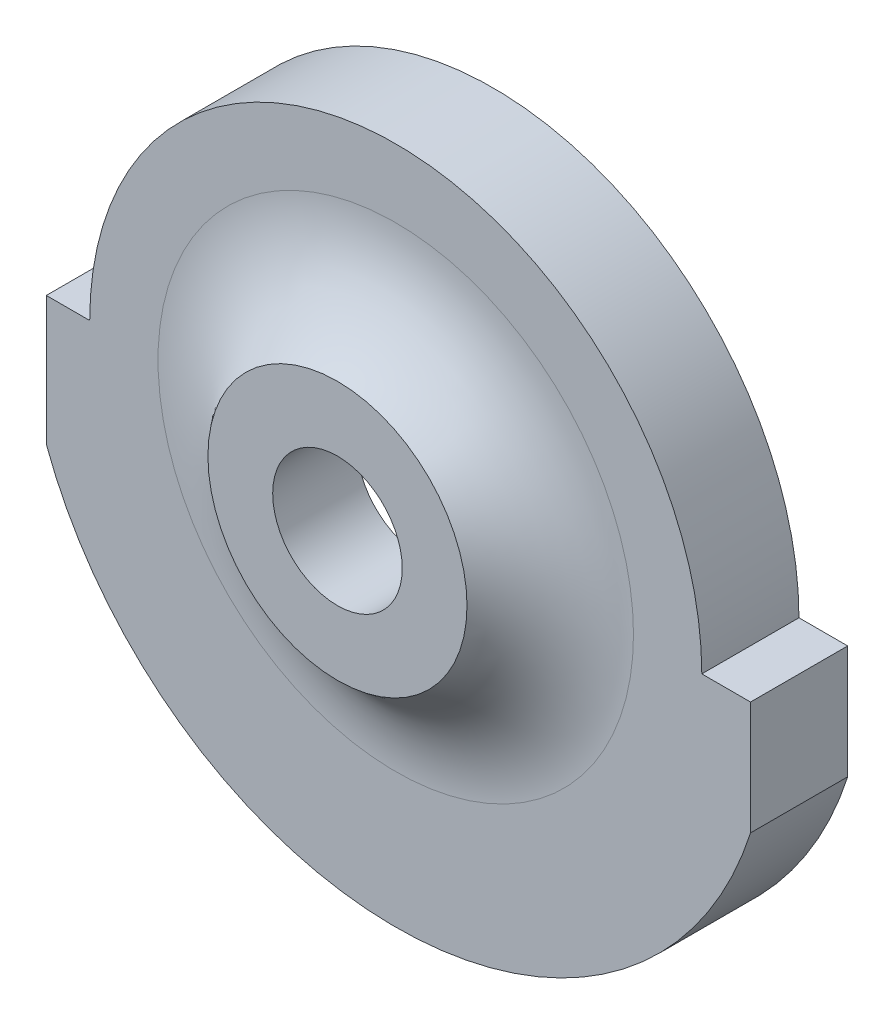
SolidWorks part; units mm, degrees
ref_plane "Front Plane" through (0, 0, 0) normal (0, 0, 1) x (1, 0, 0)
ref_plane "Top Plane" through (0, 0, 0) normal (0, 1, 0) x (1, 0, 0)
ref_plane "Right Plane" through (0, 0, 0) normal (1, 0, 0) x (0, 0, -1)
sketch "Sketch1" plane through (0, 0, 0) normal (0, 0, 1) x (1, 0, 0)
  line L0 (-8.55, 0) -> (8.55, 0) construction
  line L1 (-8.55, 0) -> (-16.55, 0)
  line L2 (8.55, 0) -> (16.55, 0)
  line L3 (-16.55, 0) -> (-16.55, 3.5)
  line L5 (-16.55, 3.5) -> (-10.9545, 3.5)
  line L6 (16.55, 0) -> (16.55, 3.5)
  line L7 (10.9545, 3.5) -> (16.55, 3.5)
  arc A0 (8.55, 0) -> (-8.55, 0) centre (0, 0) ccw
  arc A1 (10.9545, 3.5) -> (-10.9545, 3.5) centre (0, 0) ccw
  dimension "D1" = 17.1
  dimension "D3" = 23
  dimension "D2" = 3.5
extrude "Boss-Extrude1" add sketch "Sketch1" against normal blind 15.3
ref_plane "Plane1" through (0, 0, -6.3) normal (0, 0, 1) x (1, 0, 0)
sketch "Sketch2" plane through (0, 0, -6.3) normal (0, 0, 1) x (1, 0, 0)
  circle A0 centre (0, 0) radius 9.3
  dimension "D1" = 18.6
extrude "Cut-Extrude1" cut sketch "Sketch2" against normal blind 3.1
sketch "Sketch3" plane through (0, 0, 0) normal (0, 0, 1) x (1, 0, 0)
  line L0 (-10.25, 0) -> (-16.55, 0)
  line L1 (-16.55, 0) -> (-16.55, 3.5)
  line L2 (-16.55, 3.5) -> (-10.9545, 3.5)
  line L3 (10.25, 0) -> (16.55, 0)
  line L4 (16.55, 0) -> (16.55, 3.5)
  line L5 (16.55, 3.5) -> (10.9545, 3.5)
  arc A0 (10.25, 0) -> (-10.25, 0) centre (0, 0) ccw
  arc A1 (10.9545, 3.5) -> (-10.9545, 3.5) centre (0, 0) ccw
  dimension "D1" = 20.5
extrude "Boss-Extrude2" add sketch "Sketch3" along normal blind 8
sketch "Sketch4" plane through (0, 0, 8) normal (0, 0, 1) x (1, 0, 0)
  line L0 (-11.5, 0) -> (-16.55, 0)
  line L1 (-16.55, 0) -> (-16.55, 3.5)
  line L2 (-16.55, 3.5) -> (-10.9545, 3.5)
  line L3 (10.9545, 3.5) -> (16.55, 3.5)
  line L4 (16.55, 3.5) -> (16.55, 0)
  line L5 (16.55, 0) -> (11.5, 0)
  arc A0 (10.9545, 3.5) -> (-10.9545, 3.5) centre (0, 0) ccw
  arc A1 (-11.5, 0) -> (11.5, 0) centre (0, 0) ccw
  circle A2 centre (0, 0) radius 2
extrude "Boss-Extrude3" add sketch "Sketch4" along normal blind 3
sketch "Sketch5" plane through (0, 0, 11) normal (0, 0, 1) x (1, 0, 0)
  circle A1 centre (0, 0) radius 2
  circle A2 centre (0, 0) radius 4
  dimension "D1" = 8
extrude "Boss-Extrude4" add sketch "Sketch5" along normal blind 1.8
fillet "Fillet1" radius 4 1 edges at (4, 0, 11)
fillet "Fillet2" radius 1 1 edges at (0, 10.25, 8)
sketch "Sketch7" plane through (0, 0, 8) normal (0, 0, -1) x (-1, 0, 0)
  line L0 (0, 0) -> (0, -6.9122) construction
  line L1 (0, 0) -> (5.5705, 0) construction
  line L2 (5.55, 2.65) -> (5.55, -6.55)
  line L3 (-5.55, 2.65) -> (-5.55, -6.55)
  line L4 (-5.55, -6.55) -> (-3.15, -6.55)
  line L5 (-2.65, 5.55) -> (2.65, 5.55)
  line L6 (-2.65, 5.55) -> (-5.55, 2.65)
  line L7 (2.65, 5.55) -> (5.55, 2.65)
  line L8 (-3.15, -10.55) -> (3.15, -10.55)
  line L9 (-3.15, -8.55) -> (-3.15, -6.55)
  line L10 (3.15, -10.55) -> (3.15, -6.55)
  line L11 (3.15, -6.55) -> (5.55, -6.55)
  line L12 (-3.15, -10.55) -> (-6.7753, -10.55)
  line L13 (-3.15, -8.55) -> (-8.7674, -8.55)
  line L14 (-8.7674, -8.55) -> (-6.7753, -10.55)
  circle A0 centre (0, 0) radius 2
  point P6 (5.55, 5.55)
  point P13 (-5.55, 5.55)
  point P16 (0, -10.55)
  dimension "D1" = 5.55
  dimension "D2" = 6.55
  dimension "D3" = 5.55
  dimension "D4" = 6.3
  dimension "D5" = 4
extrude "Cut-Extrude2" cut sketch "Sketch7" against normal blind 2.2
sketch "Sketch8" plane through (0, 0, 8) normal (0, 0, -1) x (-1, 0, 0)
  line L0 (11.5, 0) -> (9.45, 0)
  line L1 (21.2278, -13.4753) -> (-21.2278, -13.4753)
  line L2 (21.2278, -13.4753) -> (21.2278, 13.4753)
  line L3 (21.2278, 13.4753) -> (-21.2278, 13.4753)
  line L4 (-21.2278, -13.4753) -> (-21.2278, 13.4753)
  line L5 (21.2278, -13.4753) -> (-21.2278, 13.4753) construction
  line L6 (21.2278, 13.4753) -> (-21.2278, -13.4753) construction
  line L7 (-11.5, 0) -> (-9.45, 0)
  arc A2 (9.45, 0) -> (-9.45, 0) centre (0, 0) ccw
  arc A3 (-11.5, 0) -> (11.5, 0) centre (0, 0) ccw
  dimension "D1" = 18.9
sketch "Sketch9" plane through (0, 0, 8) normal (0, 0, -1) x (-1, 0, 0)
  circle A0 centre (0, 0) radius 21.2056
extrude "Cut-Extrude4" cut sketch "Sketch9" along normal up to surface (23.3 mm away) up to face at (0, 3.8188, -15.3)
extrude "Cut-Extrude5" cut sketch "Sketch8" against normal through all
sketch "Sketch10" plane through (0, 0, 11) normal (0, 0, 1) x (1, 0, 0)
  line L0 (-10.7898, 0) -> (-10.7898, -3.9786)
  line L1 (-9.45, 0) -> (-11.5, 0) construction
  line L2 (-11.5, 0) -> (-10.7898, 0)
  line L3 (10.9545, 0) -> (10.9545, -3.5)
  line L4 (11.5, 0) -> (9.45, 0) construction
  line L5 (11.5, 0) -> (10.9545, 0)
  arc A0 (-10.7898, -3.9786) -> (-11.5, 0) centre (0, 0) cw
  arc A1 (-11.5, 0) -> (11.5, 0) centre (0, 0) ccw construction
  arc A2 (11.5, 0) -> (10.9545, -3.5) centre (0, 0) cw
extrude "Cut-Extrude6" cut sketch "Sketch10" against normal blind 10
